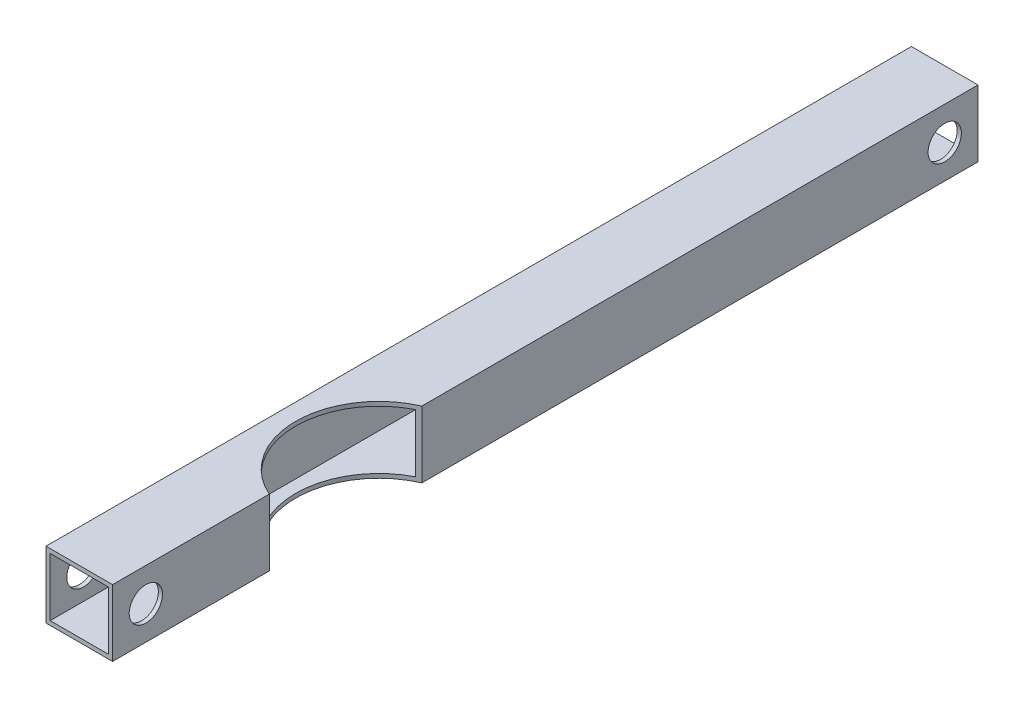
SolidWorks part; units mm, degrees
material "6061-T6 (SS)"
ref_plane "Front Plane" through (0, 0, 0) normal (0, 0, 1) x (1, 0, 0)
ref_plane "Top Plane" through (0, 0, 0) normal (0, 1, 0) x (1, 0, 0)
ref_plane "Right Plane" through (0, 0, 0) normal (1, 0, 0) x (0, 0, -1)
sketch "Sketch1" plane through (0, 0, 0) normal (0, 0, 1) x (1, 0, 0)
  line L1 (12.7, -12.7) -> (-12.7, -12.7)
  line L2 (12.7, -12.7) -> (12.7, 12.7)
  line L3 (12.7, 12.7) -> (-12.7, 12.7)
  line L4 (-12.7, -12.7) -> (-12.7, 12.7)
  line L5 (12.7, -12.7) -> (-12.7, 12.7) construction
  line L6 (12.7, 12.7) -> (-12.7, -12.7) construction
  point P0 (0, 0)
  dimension "D1" = 25.4
extrude "Extrude-Thin1" add sketch "Sketch1" along normal mid plane 330.2 thin thin type one direction reverse wall 1.5875
sketch "Sketch2" plane through (12.7, 0, 0) normal (1, 0, 0) x (0, 0, -1)
  line L0 (-152.4, 12.7) -> (-152.4, 0) construction
  line L1 (-165.1, 12.7) -> (165.1, 12.7) construction
  line L2 (-152.4, 0) -> (-152.4, -12.7) construction
  line L3 (-165.1, -12.7) -> (165.1, -12.7) construction
  line L4 (-165.1, -12.7) -> (-165.1, 12.7) construction
  line L5 (0, 12.7) -> (0, -12.7) construction
  line L6 (152.4, 0) -> (152.4, -12.7) construction
  line L7 (152.4, 12.7) -> (152.4, 0) construction
  circle A0 centre (-152.4, 0) radius 6.35
  circle A1 centre (152.4, 0) radius 6.35
  dimension "D1" = 12.7
  dimension "D2" = 12.7
extrude "Cut-Extrude1" cut sketch "Sketch2" against normal through all
sketch "Sketch3" plane through (0, -12.7, 0) normal (0, -1, 0) x (1, 0, 0)
  line L1 (12.7, 165.1) -> (12.7, -165.1) construction
  line L2 (-12.7, 165.1) -> (12.7, 165.1) construction
  circle A0 centre (25.4, 76.2) radius 31.75
  dimension "D1" = 63.5
  dimension "D2" = 12.7
  dimension "D3" = 88.9
extrude "Cut-Extrude2" cut sketch "Sketch3" against normal through all
